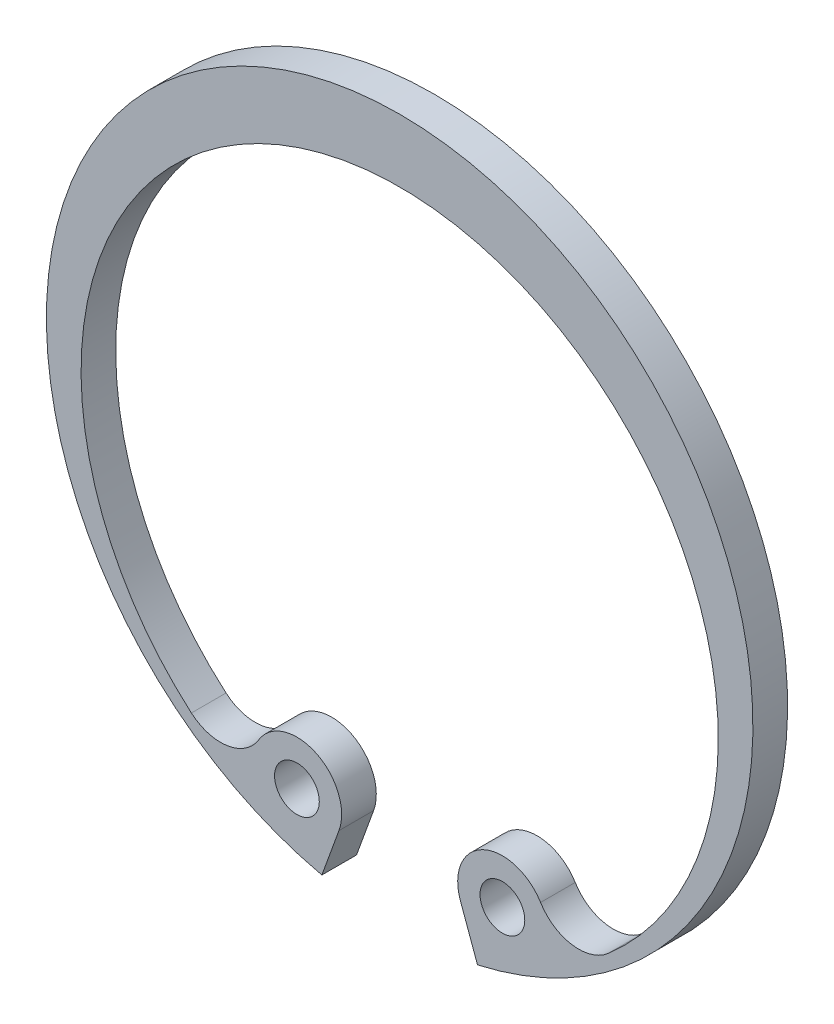
SolidWorks part; units mm, degrees
ref_plane "Front" through (0, 0, 0) normal (0, 0, 1) x (1, 0, 0)
ref_plane "Top" through (0, 0, 0) normal (0, 1, 0) x (1, 0, 0)
ref_plane "Right" through (0, 0, 0) normal (1, 0, 0) x (0, 0, -1)
ref_axis "Center Axis" through (0, 0, 1.5888) along (0, 0, -1)
sketch "Sketch1" plane through (0, 0, 0) normal (0, 0, 1) x (1, 0, 0)
  circle A0 centre (0, 0) radius 7.9
  dimension "D1" = 15.8
extrude "Extrude1" add sketch "Sketch1" along normal blind 0.775
ref_plane "Reference Plane for Front Recess" through (0, 0, 0.775) normal (0, 0, 1) x (1, 0, 0)
sketch "Sketch34" plane through (0, 0, 0.775) normal (0, 0, 1) x (1, 0, 0)
  line L0 (0, 0) -> (0, -10.6398) construction
  line L1 (0, 0) -> (-3.8763, -10.6501) construction
  line L2 (0, 0) -> (3.8763, -10.6501) construction
  line L3 (-1.3579, -6.6547) -> (-1.7405, -7.7059)
  line L4 (1.3579, -6.6547) -> (1.7405, -7.7059)
  circle A1 centre (0, 0) radius 7.9 construction
  arc A2 (1.7405, -7.7059) -> (-1.7405, -7.7059) centre (0, 0) ccw
  circle A3 centre (0, -0.635) radius 6.125 construction
  circle A4 centre (2.2976, -6.3127) radius 0.5
  circle A5 centre (-2.2976, -6.3127) radius 0.5
  arc A6 (-1.3579, -6.6547) -> (-3.1509, -5.7913) centre (-2.2976, -6.3127) ccw
  arc A7 (1.3579, -6.6547) -> (3.1509, -5.7913) centre (2.2976, -6.3127) cw
  arc A9 (-4.658, -6.0266) -> (-3.1509, -5.7913) centre (-4.0042, -5.2698) ccw
  arc A12 (4.658, -6.0266) -> (3.1509, -5.7913) centre (4.0042, -5.2698) cw
  arc A14 (4.658, -6.0266) -> (-4.658, -6.0266) centre (0, -0.635) ccw
  point P0 (0, -0.635)
  dimension "D2" = 2
  dimension "D5" = 1
  dimension "D4" = 14.25
  dimension "D1" = 0.635
  dimension "D3" = 40
extrude "056-250 Snap Ring" add sketch "Sketch34" along normal blind 0.775
sketch "Sketch35" plane through (0, 0, 0) normal (0, 0, -1) x (-1, 0, 0)
  circle A1 centre (0, 0) radius 7.9
  circle A2 centre (0, 0) radius 7.9
  dimension "D1" = 0
extrude "Cut-Extrude1" cut sketch "Sketch35" against normal blind 0.775
